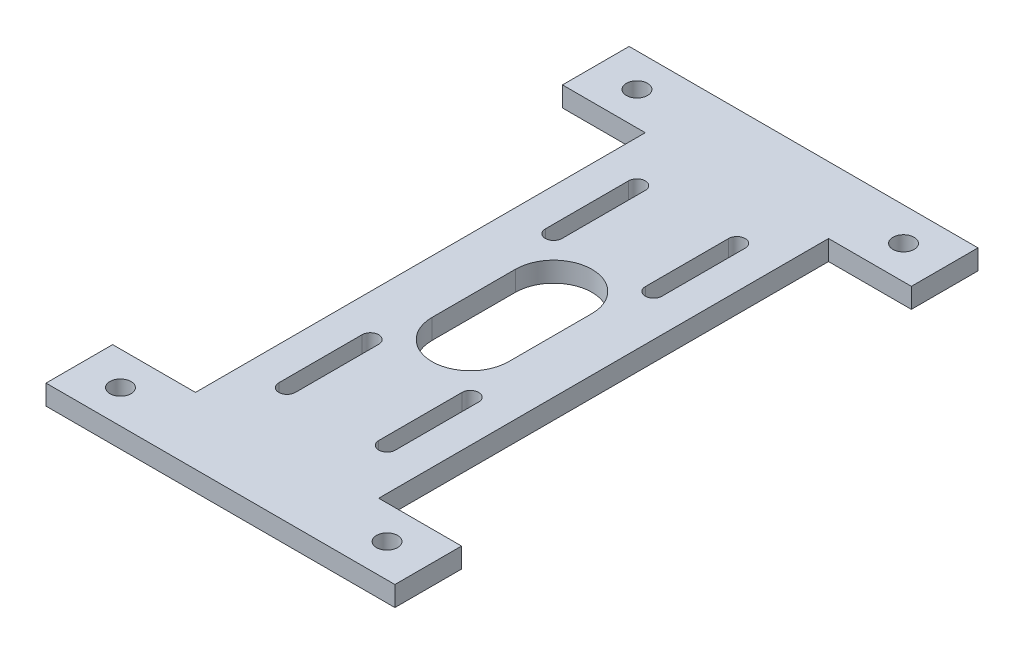
SolidWorks part; units mm, degrees
ref_plane "Front Plane" through (0, 0, 0) normal (0, 0, 1) x (1, 0, 0)
ref_plane "Top Plane" through (0, 0, 0) normal (0, 1, 0) x (1, 0, 0)
ref_plane "Right Plane" through (0, 0, 0) normal (1, 0, 0) x (0, 0, -1)
sketch "Sketch1" plane through (0, 0, 0) normal (0, 1, 0) x (1, 0, 0)
  line L0 (0, -12.5) -> (0, 12.5) construction
  line L1 (-27.5, 67.5) -> (27.5, 67.5)
  line L2 (-27.5, 67.5) -> (-27.5, -67.5)
  line L3 (-27.5, -67.5) -> (27.5, -67.5)
  line L4 (27.5, 67.5) -> (27.5, -67.5)
  line L5 (-27.5, 67.5) -> (27.5, -67.5) construction
  line L6 (-27.5, -67.5) -> (27.5, 67.5) construction
  line L7 (-11.5, -12.5) -> (-11.5, 12.5)
  line L8 (11.5, -12.5) -> (11.5, 12.5)
  line L9 (-15, -27.5) -> (-15, -52.5) construction
  line L10 (-12.5, -27.5) -> (-12.5, -52.5)
  line L11 (-17.5, -27.5) -> (-17.5, -52.5)
  line L12 (-55, 0) -> (55, 0) construction
  line L13 (-52.3534, -87.5) -> (52.3534, -87.5)
  line L14 (-52.3534, -87.5) -> (-52.3534, -67.5)
  line L15 (-52.3534, -67.5) -> (52.3534, -67.5)
  line L16 (52.3534, -87.5) -> (52.3534, -67.5)
  line L17 (-52.3534, -87.5) -> (52.3534, -67.5) construction
  line L18 (-52.3534, -67.5) -> (52.3534, -87.5) construction
  line L19 (-15, 27.5) -> (-15, 52.5) construction
  line L20 (-12.5, 27.5) -> (-12.5, 52.5)
  line L21 (-17.5, 27.5) -> (-17.5, 52.5)
  line L22 (0, -55) -> (0, 55) construction
  line L23 (15, -27.5) -> (15, -52.5) construction
  line L24 (12.5, -27.5) -> (12.5, -52.5)
  line L25 (17.5, -27.5) -> (17.5, -52.5)
  line L26 (15, 27.5) -> (15, 52.5) construction
  line L27 (12.5, 27.5) -> (12.5, 52.5)
  line L28 (17.5, 27.5) -> (17.5, 52.5)
  line L29 (-52.3534, 67.5) -> (52.3534, 67.5)
  line L30 (52.3534, 87.5) -> (52.3534, 67.5)
  line L31 (-52.3534, 87.5) -> (52.3534, 87.5)
  line L32 (-52.3534, 87.5) -> (-52.3534, 67.5)
  arc A1 (-11.5, -12.5) -> (11.5, -12.5) centre (0, -12.5) ccw
  arc A2 (11.5, 12.5) -> (-11.5, 12.5) centre (0, 12.5) ccw
  arc A3 (-12.5, -27.5) -> (-17.5, -27.5) centre (-15, -27.5) ccw
  arc A4 (-17.5, -52.5) -> (-12.5, -52.5) centre (-15, -52.5) ccw
  arc A6 (-12.5, 27.5) -> (-17.5, 27.5) centre (-15, 27.5) cw
  arc A7 (-17.5, 52.5) -> (-12.5, 52.5) centre (-15, 52.5) cw
  arc A8 (12.5, -27.5) -> (17.5, -27.5) centre (15, -27.5) cw
  arc A9 (17.5, -52.5) -> (12.5, -52.5) centre (15, -52.5) cw
  arc A10 (12.5, 27.5) -> (17.5, 27.5) centre (15, 27.5) ccw
  arc A11 (17.5, 52.5) -> (12.5, 52.5) centre (15, 52.5) ccw
  circle A12 centre (-40, -77.5) radius 3.175
  circle A13 centre (40, -77.5) radius 3.175
  circle A14 centre (40, 77.5) radius 3.175
  circle A15 centre (-40, 77.5) radius 3.175
  point P0 (0, 0)
  point P9 (0, 0)
  point P16 (-15, -40)
  point P21 (0, -77.5)
  point P30 (-15, 40)
  point P39 (15, -40)
  point P46 (15, 40)
  point P57 (-52.3534, -77.5)
  dimension "D1" = 55
  dimension "D3" = 11.5
  dimension "D5" = 2.5
  dimension "D9" = 6.35
  dimension "D2" = 135
  dimension "D4" = 25
  dimension "D6" = 20
  dimension "D7" = 40
  dimension "D8" = 15
  dimension "D10" = 40
extrude "Boss-Extrude1" add sketch "Sketch1" along normal blind 6 contours L13 L16 L15 L3 L14 | L4 L1 L2 L3 A4 L11 A3 L10 A2 L8 A1 L7 | L31 L32 L29 L1 L30 A14 A15 region at (0, 0, -77.5) region at (0, 0, -66.0423) region at (0, 0, 77.5)
sketch "Sketch2" plane through (0, 0, 0) normal (0, 1, 0) x (1, 0, 0)
  line L0 (0, -3.3) -> (0, 3.3) construction
  line L1 (-3.3, 0) -> (3.3, 0) construction
  circle A0 centre (-40, 77.5) radius 6
  circle A1 centre (40, 77.5) radius 6
  circle A2 centre (40, -77.5) radius 6
  circle A3 centre (-40, -77.5) radius 6
  dimension "D1" = 12
extrude "Cut-Extrude1" cut sketch "Sketch2" along normal blind 1.5
